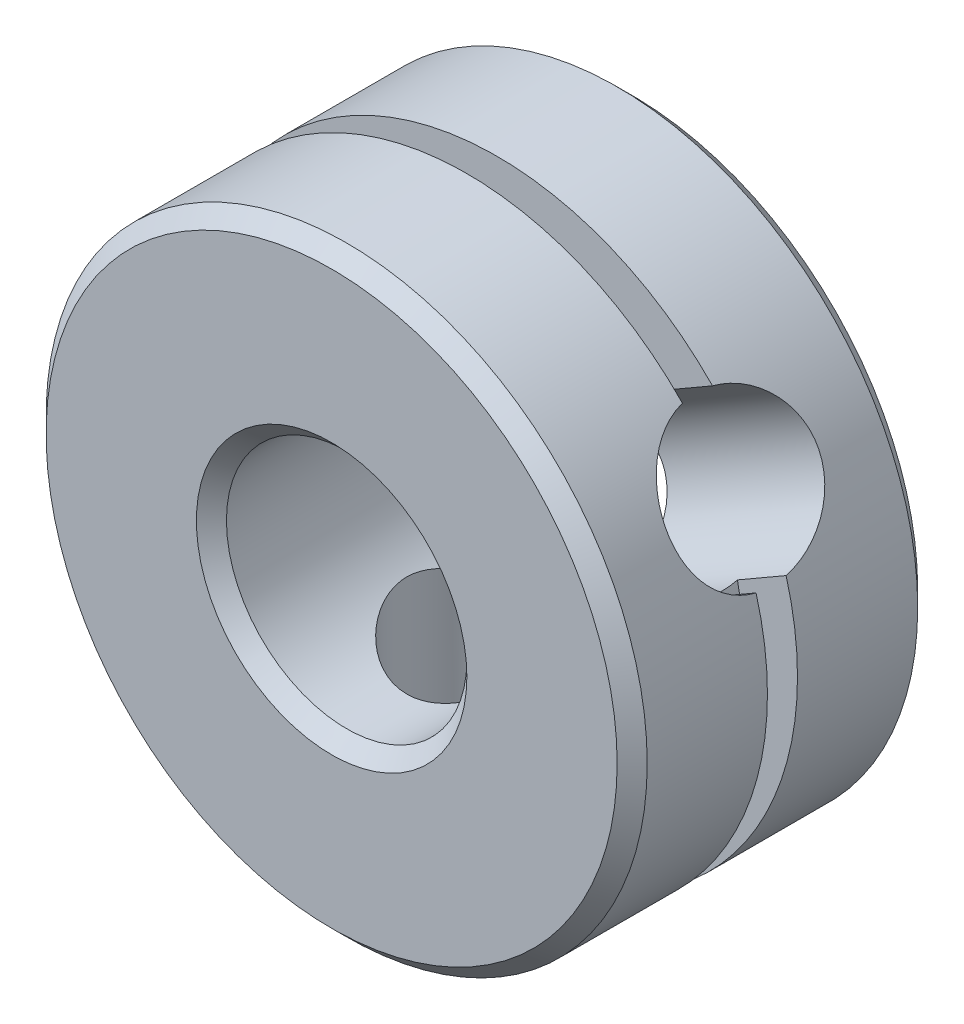
SolidWorks part; units mm, degrees
ref_plane "Front" through (0, 0, 0) normal (0, 0, 1) x (1, 0, 0)
ref_plane "Top" through (0, 0, 0) normal (0, 1, 0) x (1, 0, 0)
ref_plane "Right" through (0, 0, 0) normal (1, 0, 0) x (0, 0, -1)
sketch "Sketch1" plane through (0, 0, 0) normal (0, 0, 1) x (1, 0, 0)
  circle A0 centre (0, 0) radius 10
  circle A1 centre (0, 0) radius 4
  dimension "d" = 8
  dimension "D0" = 20
extrude "Base-Extrude" add sketch "Sketch1" against normal blind 10
chamfer "Chamfer1" distance 0.5 angle 45 2 edges at (10, 0, -10) (10, 0, 0)
sketch "Sketch2" plane through (0, 0, 0) normal (0, 1, 0) x (1, 0, 0)
  line L0 (9.5, 10) -> (-9.5, 10) construction
  line L1 (0, 3.5505) -> (0, -10.3547) construction
  circle A0 centre (0, 5) radius 2.5
  dimension "H/2" = 5
extrude "Hole" cut sketch "Sketch2" against normal through all
pattern_circular "HolePat" count 2 every 120 about axis through (0, 0, -10) along (0, 0, 1) of "Hole"
chamfer "EndChamfer" distance 0.5 angle 45 2 edges at (4, 0, -10) (4, 0, 0)
sketch "Sketch3" plane through (0, 0, 0) normal (0, 1, 0) x (1, 0, 0)
  line L1 (-10, 5.5) -> (-8.2, 5.5)
  line L2 (-10, 5.5) -> (-10, 4.5)
  line L3 (-10, 4.5) -> (-8.2, 4.5)
  line L4 (-8.2, 5.5) -> (-8.2, 4.5)
  line L6 (0, 2.3593) -> (0, -11.0317) construction
  line L8 (9.5, 10) -> (-9.5, 10) construction
  line L9 (-10, 9.5) -> (-10, 0.5) construction
  dimension "D2" = 4.5
revolve "Slot" cut sketch "Sketch3" angle 360 about L6
equation "\"H/2@Sketch2\" = \"H@Base-Extrude\" / 2"
equation "\"D2@Sketch3\" =  ( \"H@Base-Extrude\"  - \"b@Sketch3\" ) / 2"
